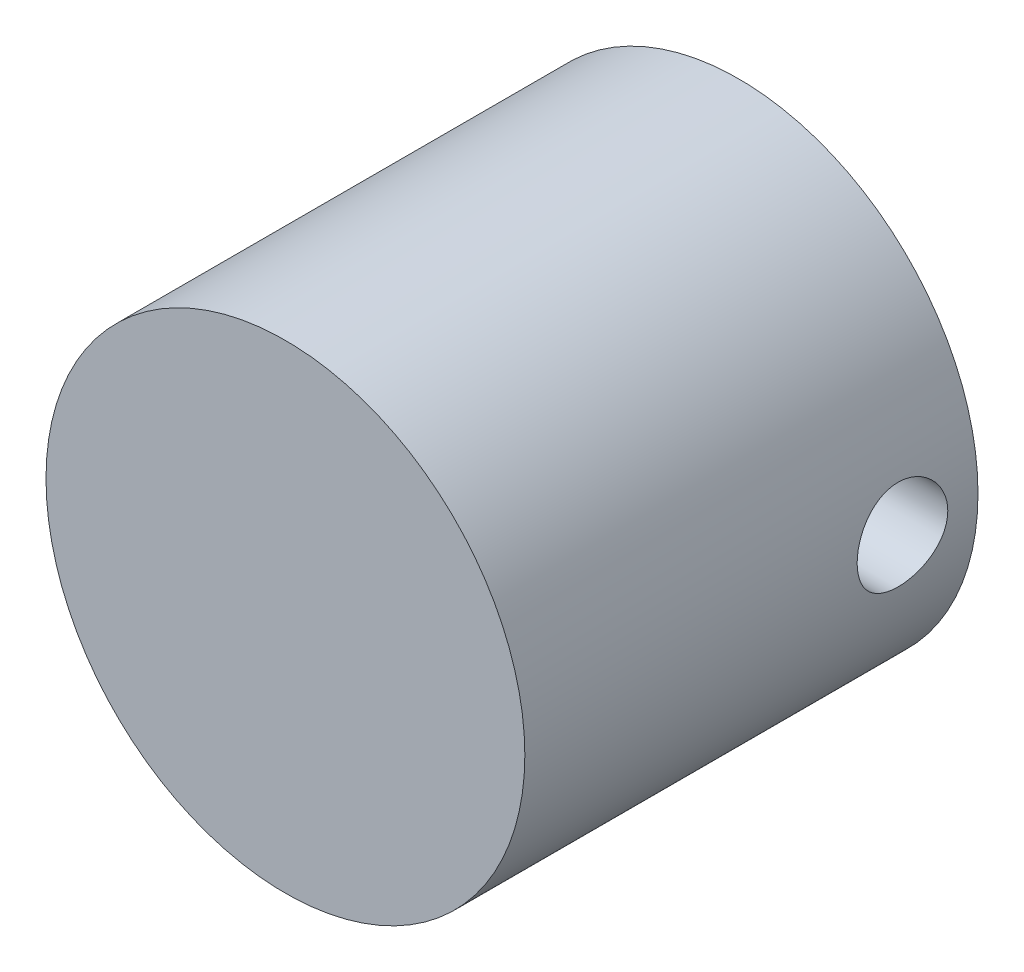
SolidWorks part; units mm, degrees
ref_plane "Front" through (0, 0, 0) normal (0, 0, 1) x (1, 0, 0)
ref_plane "Top" through (0, 0, 0) normal (0, 1, 0) x (1, 0, 0)
ref_plane "Right" through (0, 0, 0) normal (1, 0, 0) x (0, 0, -1)
sketch "Sketch1" plane through (0, 0, 0) normal (0, 0, 1) x (1, 0, 0)
  circle A0 centre (0, 0) radius 7.925
extrude "Extrude1" add sketch "Sketch1" along normal blind 15
sketch "Sketch2" plane through (0, 0, 0) normal (1, 0, 0) x (0, 0, -1)
  line L0 (-15, 0) -> (0, 0) construction
  circle A0 centre (-2.5, 0) radius 1.5
extrude "Cut-Extrude1" cut sketch "Sketch2" against normal through all and the other way through all
